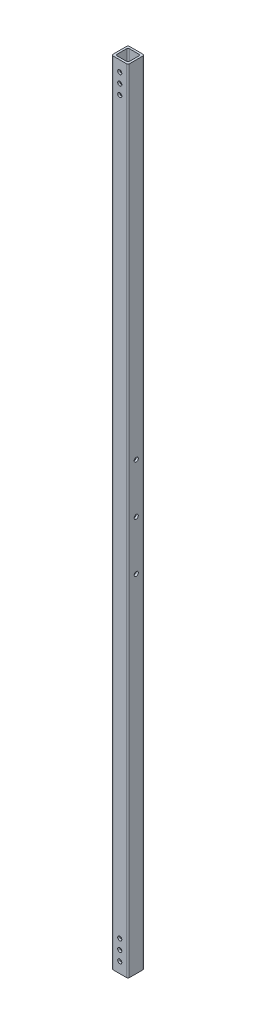
SolidWorks part; units mm, degrees
material "6061-T6 (SS)"
ref_plane "Front Plane" through (0, 0, 0) normal (0, 0, 1) x (1, 0, 0)
ref_plane "Top Plane" through (0, 0, 0) normal (0, 1, 0) x (1, 0, 0)
ref_plane "Right Plane" through (0, 0, 0) normal (1, 0, 0) x (0, 0, -1)
sketch "Sketch1" plane through (0, 0, 0) normal (0, 1, 0) x (1, 0, 0)
  line L0 (9.525, 9.525) -> (-9.525, 9.525)
  line L1 (12.7, -12.7) -> (-12.7, -12.7)
  line L2 (12.7, -12.7) -> (12.7, 12.7)
  line L3 (12.7, 12.7) -> (-12.7, 12.7)
  line L4 (-12.7, -12.7) -> (-12.7, 12.7)
  line L5 (12.7, -12.7) -> (-12.7, 12.7) construction
  line L6 (12.7, 12.7) -> (-12.7, -12.7) construction
  line L7 (-9.525, -9.525) -> (-9.525, 9.525)
  line L8 (9.525, -9.525) -> (-9.525, -9.525)
  line L9 (9.525, -9.525) -> (9.525, 9.525)
  point P0 (0, 0)
  dimension "D1" = 25.4
  dimension "D2" = 25.4
  dimension "D3" = 3.175
extrude "Boss-Extrude1" add sketch "Sketch1" along normal mid plane 1219.2
fillet "Fillet1" radius 2.1082 8 edges at (9.525, 0, -9.525) (-9.525, 0, -9.525) (-9.525, 0, 9.525) (9.525, 0, 9.525) (12.7, 0, -12.7) (-12.7, 0, -12.7) (-12.7, 0, 12.7) (12.7, 0, 12.7)
sketch "Sketch6" plane through (0, 0, -12.7) normal (0, 0, -1) x (-1, 0, 0)
  line L0 (0, 609.6) -> (0, 600.8737) construction
  line L2 (0, 402.295) -> (0, -606.425) construction
  line L3 (-10.5918, 609.6) -> (10.5918, 609.6) construction
  line L7 (0, 0) -> (10.5918, 0) construction
  line L8 (10.5918, -609.6) -> (10.5918, 609.6) construction
  line L9 (0, 609.6) -> (0, 558.8) construction
  circle A12 centre (0, 562.61) radius 3.175
  circle A13 centre (0, 577.85) radius 3.175
  circle A14 centre (0, 593.09) radius 3.175
  point P29 (0, 562.61)
  point P31 (0, 577.85)
  point P32 (0, 593.09)
  dimension "D1" = 15.24
  dimension "D2" = 15.24
  dimension "D3" = 16.51
  dimension "D7" = 50.8
extrude "Cut-Extrude5" cut sketch "Sketch6" against normal through all
sketch "Sketch7" plane through (-12.7, 0, 0) normal (-1, 0, 0) x (0, 0, 1)
  circle A0 centre (0, 0) radius 3.175
  dimension "D1" = 6.35
extrude "Cut-Extrude6" cut sketch "Sketch7" against normal through all
sketch "Sketch8" plane through (-12.7, 0, 0) normal (-1, 0, 0) x (0, 0, 1)
  line L0 (0, 0) -> (0, -76.2) construction
  circle A0 centre (0, -76.2) radius 3.175
  dimension "D2" = 6.35
  dimension "D1" = 76.2
extrude "Cut-Extrude7" cut sketch "Sketch8" against normal through all
mirror "Mirror1" about plane through (0, 0, 0) normal (0, 1, 0) of "Cut-Extrude7"
mirror "Mirror2" about plane through (0, 0, 0) normal (0, 1, 0) of "Cut-Extrude5"
